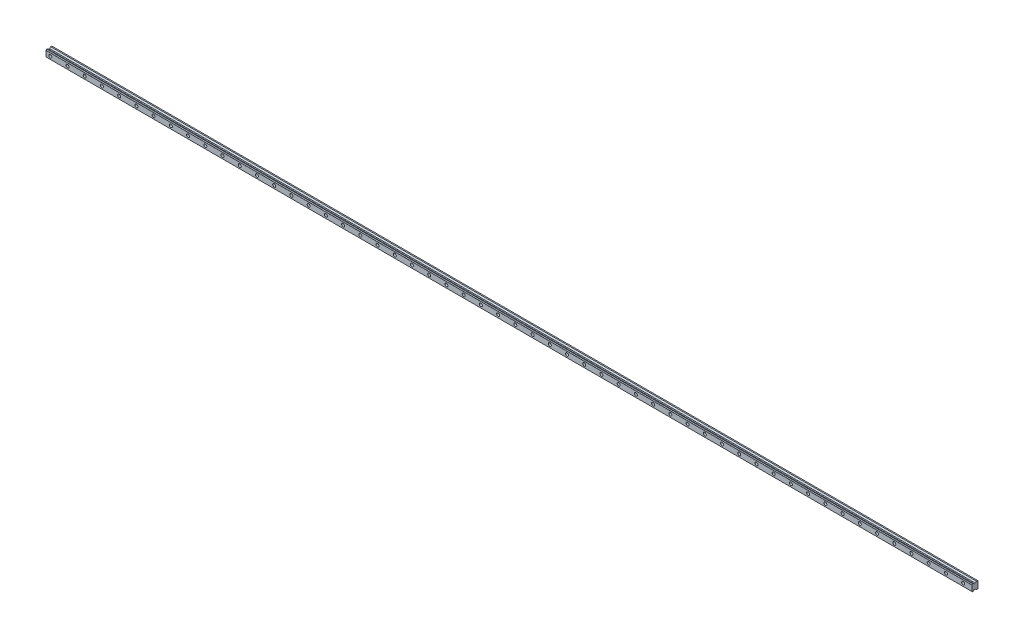
SolidWorks part; units mm, degrees
ref_plane "Front Plane" through (0, 0, 0) normal (0, 0, 1) x (1, 0, 0)
ref_plane "Top Plane" through (0, 0, 0) normal (0, 1, 0) x (1, 0, 0)
ref_plane "Right Plane" through (0, 0, 0) normal (1, 0, 0) x (0, 0, -1)
ref_plane "Plane1" through (0, 0, 0) normal (0, 0, -1) x (-1, 0, 0)
sketch "Sketch1" plane through (0, 0, 0) normal (0, 0, -1) x (-1, 0, 0)
  line L0 (-180, 17) -> (-180, -17)
  line L1 (-180, -17) -> (20, -17)
  line L2 (20, -17) -> (20, 17)
  line L3 (20, 17) -> (-180, 17)
extrude "Boss-Extrude1" add sketch "Sketch1" against normal blind 29
sketch "Sketch2" plane through (180, 0, 0) normal (1, 0, 0) x (0, 0, -1)
  line L0 (0, -8.25) -> (0, -3.75)
  line L1 (0, -3.75) -> (-0.5, -3.75)
  line L2 (-0.5, -3.75) -> (-0.5, -8.25)
  line L3 (-0.5, -8.25) -> (0, -8.25)
extrude "Cut-Extrude1" cut sketch "Sketch2" against normal through all
sketch "Sketch3" plane through (180, 0, 0) normal (1, 0, 0) x (0, 0, -1)
  line L0 (-22.3687, -17) -> (-12.2, -17)
  line L1 (-12.2, -17) -> (-12.2, -11.8)
  line L2 (-12.2, -11.8) -> (-17.68, -11.8)
  line L3 (-17.68, -11.8) -> (-19.5325, -13.6525)
  arc A0 (-19.5325, -13.6525) -> (-22.3687, -17) centre (-19.1314, -16.8676) ccw
extrude "Cut-Extrude2" cut sketch "Sketch3" against normal through all
sketch "Sketch4" plane through (180, 0, 0) normal (1, 0, 0) x (0, 0, -1)
  line L0 (-7, 17) -> (-22.3687, 17)
  line L1 (-19.5325, 13.6525) -> (-17.68, 11.8)
  line L2 (-17.68, 11.8) -> (-7, 11.8)
  line L3 (-7, 11.8) -> (-7, 17)
  arc A0 (-22.3687, 17) -> (-19.5325, 13.6525) centre (-19.1314, 16.8676) ccw
extrude "Cut-Extrude3" cut sketch "Sketch4" against normal through all
sketch "Sketch5" plane through (180, 0, 0) normal (1, 0, 0) x (0, 0, -1)
  line L0 (0, 8.25) -> (-0.5, 8.25)
  line L1 (-0.5, 8.25) -> (-0.5, 3.75)
  line L2 (-0.5, 3.75) -> (0, 3.75)
  line L3 (0, 3.75) -> (0, 8.25)
extrude "Cut-Extrude4" cut sketch "Sketch5" against normal through all
draft "Draft1" type of draft neutral plane draft angle 45 faces to draft 1 face at (80, 14.4, 7) neutral plane through (-20, 17, 29) neutral plane normal (0, 1, 0) parameters "D1"=45
draft "Draft2" type of draft neutral plane draft angle 45 faces to draft 1 face at (80, -14.4, 12.2) neutral plane through (-20, -11.8, 12.2) neutral plane normal (0, -1, 0) parameters "D1"=45
draft "Draft3" type of draft neutral plane draft angle 45 faces to draft 2 face at (80, 8.25, 0.25) face at (80, 3.75, 0.25) neutral plane through (-20, 8.25, 0.5) neutral plane normal (0, 0, -1) parameters "D1"=45
draft "Draft4" type of draft neutral plane draft angle 45 faces to draft 2 face at (80, -8.25, 0.25) face at (80, -3.75, 0.25) neutral plane through (-20, -3.75, 0.5) neutral plane normal (0, 0, -1) parameters "D1"=45
hole_wizard "M6 Clearance Hole1" positions "Sketch7" profile "Sketch6" hole size "M6" standard "ANSI Metric"
sketch "Sketch7" plane through (-20, 0, 0) normal (-1, 0, 0) x (0, 0, 1)
  point P0 (28.8696, -16.8676)
  point P1 (28.8696, 16.8676)
sketch "Sketch6" plane through (-20, -16.8676, 28.8696) normal (0, 1, 0) x (0, 0, 1)
  line L0 (0, 0) -> (0, 200)
  line L1 (0, 200) -> (3.24, 200)
  line L2 (3.24, 200) -> (3.24, 0)
  line L5 (3.24, 0) -> (0, 0)
  line L11 (0, -6.35) -> (0, 107.95) construction
  dimension "Thru Hole Dia." = 6.48
  dimension "Thru Hole Depth" = 200
hole_wizard "CBORE for M8 Hex Head Bolt1" positions "Sketch9" profile "Sketch8" counterbore size "M8" standard "ANSI Metric"
sketch "Sketch9" plane through (0, 0, 29) normal (0, 0, 1) x (1, 0, 0)
  point P0 (80, 0)
  point P1 (160, 0)
  point P2 (0, 0)
sketch "Sketch8" plane through (80, 0, 29) normal (1, 0, 0) x (0, -1, 0)
  line L0 (0, 0) -> (0, 29)
  line L1 (0, 29) -> (4.5, 29)
  line L3 (4.5, 29) -> (4.5, 12)
  line L4 (4.5, 12) -> (7, 12)
  line L5 (7, 12) -> (7, 0)
  line L7 (7, 0) -> (0, 0)
  line L11 (0, -6.35) -> (0, 107.95) construction
  dimension "Thru Hole Dia." = 9
  dimension "Thru Hole Depth" = 29
  dimension "C'Bore Dia." = 14
  dimension "C'Bore Depth" = 12
chamfer "Chamfer1" distance 0.4758 angle 45 6 edges at (80, 13.6302, 29) (80, 17, 22.3687) (80, -17, 22.3687) (80, -13.6302, 29) (80, -17, 25.6323) (80, 17, 25.6323) first distance on face at (80, 14.9462, 26.947) first distance on face at (80, 17, 24.0005) first distance on face at (80, -15.0497, 21.277) first distance on face at (80, -14.9462, 26.947) first distance on face at (80, -17, 24.0005)
chamfer "Chamfer2" distance 1.5 angle 45 2 edges at (80, 17, 0) (80, -17, 0)
sketch "Sketch10" plane through (180, 0, 0) normal (1, 0, 0) x (0, 0, -1)
  line L28 (0, 8.75) -> (0, 15.5)
  line L29 (0, 15.5) -> (-1.5, 17)
  line L30 (-1.5, 17) -> (-7, 17)
  line L31 (-7, 17) -> (-12.2, 11.8)
  line L32 (-12.2, 11.8) -> (-17.68, 11.8)
  line L33 (-17.68, 11.8) -> (-19.5325, 13.6525)
  line L34 (-22.3513, 16.5068) -> (-22.8445, 17)
  line L35 (-22.8445, 17) -> (-25.1565, 17)
  line L36 (-25.1565, 17) -> (-25.6497, 16.5068)
  line L37 (-28.4814, 13.6509) -> (-29, 13.1725)
  line L38 (-29, 13.1725) -> (-29, -13.1725)
  line L39 (-29, -13.1725) -> (-28.4814, -13.6509)
  line L40 (-25.6497, -16.5068) -> (-25.1565, -17)
  line L41 (-25.1565, -17) -> (-22.8262, -17)
  line L42 (-22.8262, -17) -> (-22.3483, -16.4814)
  line L43 (-19.5325, -13.6525) -> (-17.68, -11.8)
  line L44 (-17.68, -11.8) -> (-12.2, -11.8)
  line L45 (-12.2, -11.8) -> (-7, -17)
  line L46 (-7, -17) -> (-1.5, -17)
  line L47 (-1.5, -17) -> (0, -15.5)
  line L48 (0, -15.5) -> (0, -8.75)
  line L49 (0, -8.75) -> (-0.5, -8.25)
  line L50 (-0.5, -8.25) -> (-0.5, -3.75)
  line L51 (-0.5, -3.75) -> (0, -3.25)
  line L52 (0, -3.25) -> (0, 3.25)
  line L53 (0, 3.25) -> (-0.5, 3.75)
  line L54 (-0.5, 3.75) -> (-0.5, 8.25)
  line L55 (-0.5, 8.25) -> (0, 8.75)
  line L56 (0, 8.75) -> (0, 15.5)
  line L57 (0, 15.5) -> (-1.5, 17)
  line L58 (-1.5, 17) -> (-7, 17)
  line L59 (-7, 17) -> (-12.2, 11.8)
  line L60 (-12.2, 11.8) -> (-17.68, 11.8)
  line L61 (-17.68, 11.8) -> (-19.5325, 13.6525)
  line L62 (-22.3513, 16.5068) -> (-22.8445, 17)
  line L63 (-22.8445, 17) -> (-25.1565, 17)
  line L64 (-25.1565, 17) -> (-25.6497, 16.5068)
  line L65 (-28.4814, 13.6509) -> (-29, 13.1725)
  line L66 (-29, 13.1725) -> (-29, -13.1725)
  line L67 (-29, -13.1725) -> (-28.4814, -13.6509)
  line L68 (-25.6497, -16.5068) -> (-25.1565, -17)
  line L69 (-25.1565, -17) -> (-22.8262, -17)
  line L70 (-22.8262, -17) -> (-22.3483, -16.4814)
  line L71 (-19.5325, -13.6525) -> (-17.68, -11.8)
  line L72 (-17.68, -11.8) -> (-12.2, -11.8)
  line L73 (-12.2, -11.8) -> (-7, -17)
  line L74 (-7, -17) -> (-1.5, -17)
  line L75 (-1.5, -17) -> (0, -15.5)
  line L76 (0, -15.5) -> (0, -8.75)
  line L77 (0, -8.75) -> (-0.5, -8.25)
  line L78 (-0.5, -8.25) -> (-0.5, -3.75)
  line L79 (-0.5, -3.75) -> (0, -3.25)
  line L80 (0, -3.25) -> (0, 3.25)
  line L81 (0, 3.25) -> (-0.5, 3.75)
  line L82 (-0.5, 3.75) -> (-0.5, 8.25)
  line L83 (-0.5, 8.25) -> (0, 8.75)
  arc A4 (-22.3513, 16.5068) -> (-19.5325, 13.6525) centre (-19.1314, 16.8676) ccw
  arc A5 (-28.4814, 13.6509) -> (-25.6497, 16.5068) centre (-28.8696, 16.8676) ccw
  arc A6 (-25.6497, -16.5068) -> (-28.4814, -13.6509) centre (-28.8696, -16.8676) ccw
  arc A7 (-19.5325, -13.6525) -> (-22.3483, -16.4814) centre (-19.1314, -16.8676) ccw
  arc A8 (-22.3513, 16.5068) -> (-19.5325, 13.6525) centre (-19.1314, 16.8676) ccw
  arc A9 (-28.4814, 13.6509) -> (-25.6497, 16.5068) centre (-28.8696, 16.8676) ccw
  arc A10 (-25.6497, -16.5068) -> (-28.4814, -13.6509) centre (-28.8696, -16.8676) ccw
  arc A11 (-19.5325, -13.6525) -> (-22.3483, -16.4814) centre (-19.1314, -16.8676) ccw
  dimension "D1" = 0
extrude "Boss-Extrude4" add sketch "Sketch10" along normal blind 4100
pattern_linear "LPattern1" count 52 spacing 80 along (1, 0, 0) of "CBORE for M8 Hex Head Bolt1"
